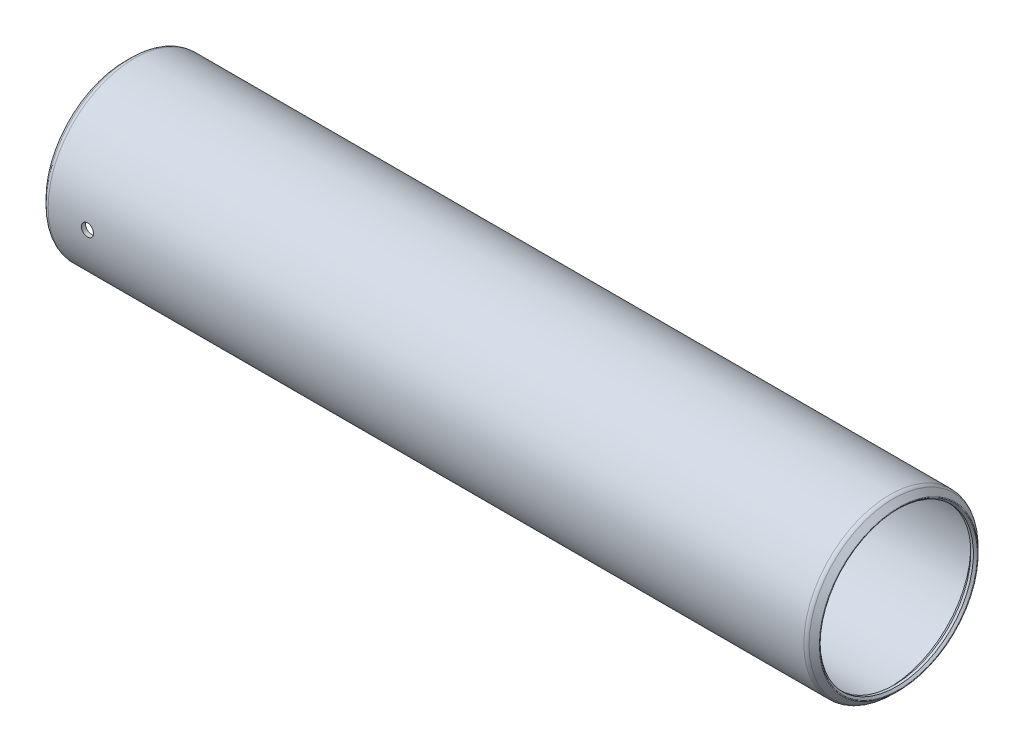
SolidWorks part; units mm, degrees
ref_plane "Front Plane" through (0, 0, 0) normal (0, 0, 1) x (1, 0, 0)
ref_plane "Top Plane" through (0, 0, 0) normal (0, 1, 0) x (1, 0, 0)
ref_plane "Right Plane" through (0, 0, 0) normal (1, 0, 0) x (0, 0, -1)
ref_plane "Plane1" through (149.5552, 0, 0) normal (1, 0, 0) x (0, 0, -1)
sketch "Sketch1" plane through (0, 0, 0) normal (0, 0, 1) x (1, 0, 0)
  line L0 (-0.8826, 15.3797) -> (-0.508, 15.0051)
  line L1 (-0.508, 15.0051) -> (0, 15.0051)
  line L2 (0, 15.0051) -> (1.016, 16.021)
  line L3 (1.016, 16.021) -> (148.5392, 16.021)
  line L4 (148.5392, 16.021) -> (149.5552, 15.0051)
  line L5 (149.5552, 15.0051) -> (150.0632, 15.0051)
  line L6 (150.0632, 15.0051) -> (150.4378, 15.3797)
  line L7 (150.4378, 15.5593) -> (149.4481, 16.549)
  line L8 (148.7297, 16.8465) -> (0.8255, 16.8465)
  line L9 (0.1071, 16.549) -> (-0.8826, 15.5593)
  line L10 (149.5552, 0) -> (0, 0) construction
  arc A0 (-0.8826, 15.5593) -> (-0.8826, 15.3797) centre (-0.7928, 15.4695) ccw
  arc A1 (150.4378, 15.3797) -> (150.4378, 15.5593) centre (150.348, 15.4695) ccw
  arc A2 (149.4481, 16.549) -> (148.7297, 16.8465) centre (148.7297, 15.8305) ccw
  arc A3 (0.8255, 16.8465) -> (0.1071, 16.549) centre (0.8255, 15.8305) ccw
revolve "Revolve1" add sketch "Sketch1" angle 360 about L10 reverse direction yes
sketch "Sketch2" plane through (0, 0, 0) normal (0, 0, 1) x (1, 0, 0)
  circle A0 centre (8.509, 0) radius 1.1938
extrude "Cut-Extrude1" cut sketch "Sketch2" along normal blind 16.8466
ref_plane "Plane2" through (74.7776, 0, 0) normal (1, 0, 0) x (0, 0, -1)
ref_plane "cp1 XY" through (74.7776, 0, 0) normal (1, 0, 0) x (0, 0, -1)
ref_plane "cp1 XZ" through (0, 16.8466, 0) normal (0, -1, 0) x (-1, 0, 0)
ref_plane "cp1 YZ" through (0, 0, 0) normal (0, 0, -1) x (-1, 0, 0)
ref_axis "cp1 X" through (74.7776, 16.8466, 80.9) along (0, 0, -1)
ref_axis "cp1 Y" through (74.7776, -50, 0) along (0, 1, 0)
ref_axis "cp1 Z" through (80.9, 16.8466, 0) along (-1, 0, 0)
sketch3d "cp1"
  point P0 (74.7776, 16.8466, 0)
ref_plane "cp2 XY" through (74.7776, 0, 0) normal (1, 0, 0) x (0, 0, -1)
ref_plane "cp2 XZ" through (0, 0, 0) normal (0, -1, 0) x (-1, 0, 0)
ref_plane "cp2 YZ" through (0, 0, -16.8466) normal (0, 0, -1) x (-1, 0, 0)
ref_axis "cp2 X" through (74.7776, 0, 80.9) along (0, 0, -1)
ref_axis "cp2 Y" through (74.7776, -50, -16.8466) along (0, 1, 0)
ref_axis "cp2 Z" through (80.9, 0, -16.8466) along (-1, 0, 0)
sketch3d "cp2"
  point P0 (74.7776, 0, -16.8466)
ref_plane "cp3 XY" through (74.7776, 0, 0) normal (1, 0, 0) x (0, 0, -1)
ref_plane "cp3 XZ" through (0, -16.8466, 0) normal (0, -1, 0) x (-1, 0, 0)
ref_plane "cp3 YZ" through (0, 0, 0) normal (0, 0, -1) x (-1, 0, 0)
ref_axis "cp3 X" through (74.7776, -16.8466, 80.9) along (0, 0, -1)
ref_axis "cp3 Y" through (74.7776, -50, 0) along (0, 1, 0)
ref_axis "cp3 Z" through (80.9, -16.8466, 0) along (-1, 0, 0)
sketch3d "cp3"
  point P0 (74.7776, -16.8466, 0)
ref_plane "cp4 XY" through (74.7776, 0, 0) normal (1, 0, 0) x (0, 0, -1)
ref_plane "cp4 XZ" through (0, 0, 0) normal (0, -1, 0) x (-1, 0, 0)
ref_plane "cp4 YZ" through (0, 0, 16.8466) normal (0, 0, -1) x (-1, 0, 0)
ref_axis "cp4 X" through (74.7776, 0, 80.9) along (0, 0, -1)
ref_axis "cp4 Y" through (74.7776, -50, 16.8466) along (0, 1, 0)
ref_axis "cp4 Z" through (80.9, 0, 16.8466) along (-1, 0, 0)
sketch3d "cp4"
  point P0 (74.7776, 0, 16.8466)
ref_plane "tube_front XY" through (0, 0, 0) normal (1, 0, 0) x (0, 0, -1)
ref_plane "tube_front XZ" through (0, 0, 0) normal (0, -1, 0) x (-1, 0, 0)
ref_plane "tube_front YZ" through (0, 0, 0) normal (0, 0, -1) x (-1, 0, 0)
ref_axis "tube_front X" through (0, 0, 80.9) along (0, 0, -1)
ref_axis "tube_front Y" through (0, -50, 0) along (0, 1, 0)
ref_axis "tube_front Z" through (80.9, 0, 0) along (-1, 0, 0)
sketch3d "tube_front"
  point P0 (0, 0, 0)
ref_plane "tube_rear XY" through (149.5552, 0, 0) normal (1, 0, 0) x (0, 0, -1)
ref_plane "tube_rear XZ" through (0, 0, 0) normal (0, -1, 0) x (-1, 0, 0)
ref_plane "tube_rear YZ" through (0, 0, 0) normal (0, 0, -1) x (-1, 0, 0)
ref_axis "tube_rear X" through (149.5552, 0, 80.9) along (0, 0, -1)
ref_axis "tube_rear Y" through (149.5552, -50, 0) along (0, 1, 0)
ref_axis "tube_rear Z" through (80.9, 0, 0) along (-1, 0, 0)
sketch3d "tube_rear"
  point P0 (149.5552, 0, 0)
